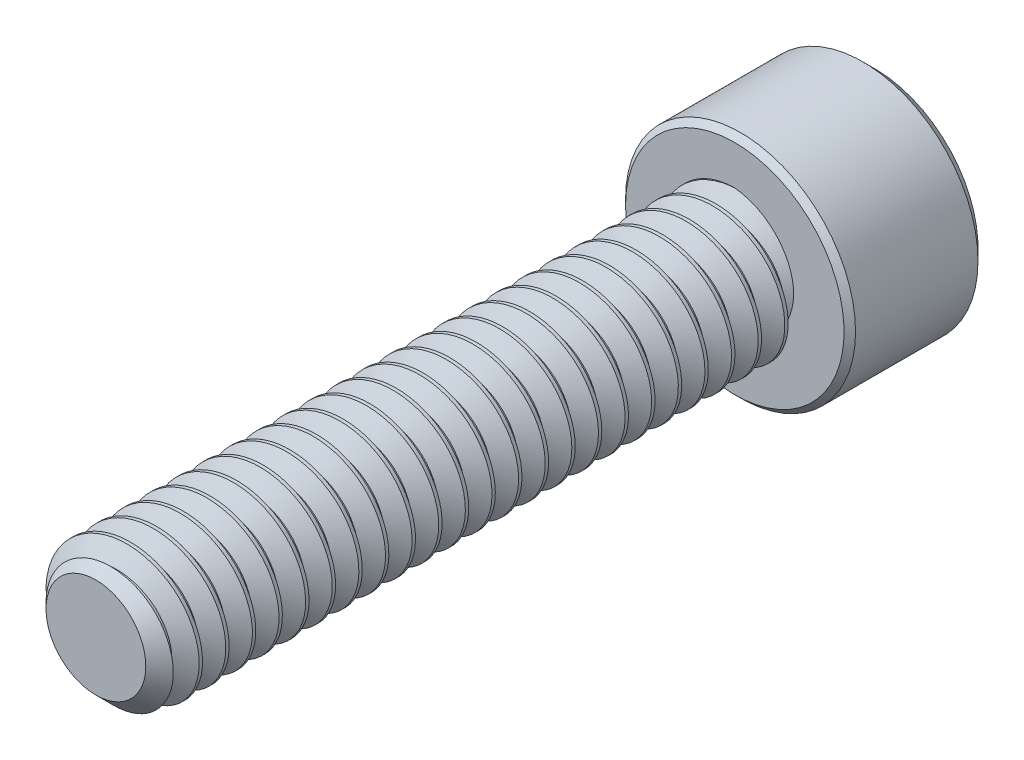
SolidWorks part; units mm, degrees
ref_plane "Front Plane" through (0, 0, 0) normal (0, 0, 1) x (1, 0, 0)
ref_plane "Top Plane" through (0, 0, 0) normal (0, 1, 0) x (1, 0, 0)
ref_plane "Right Plane" through (0, 0, 0) normal (1, 0, 0) x (0, 0, -1)
sketch "Sketch0" plane through (0, 0, 0) normal (1, 0, 0) x (0, 0, -1)
  line L0 (0, 0) -> (19.05, 0) construction
  point P2 (23.2156, 0)
  point P4 (0, 0)
  dimension "D1" = 19.05
  dimension "D2" = 4.1656
  dimension "Min Thread" = 0
sketch "Sketch1" plane through (0, 0, 0) normal (0, 0, 1) x (1, 0, 0)
  circle A0 centre (0, 0) radius 2.0828
  dimension "OD" = 4.1656
extrude "Extrude1" add sketch "Sketch1" against normal blind 19.05
sketch "Sketch2" plane through (0, 0, 0) normal (0, 0, 1) x (1, 0, 0)
  circle A0 centre (0, 0) radius 2.0828 construction
  circle A1 centre (0, 0) radius 2.0828
curve "Helix/Spiral1" pitch 0.7937 height 19.8438 turns 25 parameters "pitch"=0.7937
chamfer "Chamfer3" distance 0.5953 angle 45 1 edges at (2.0828, 0, 0)
sketch "Sketch3" plane through (0, 0, 0) normal (1, 0, 0) x (0, 0, -1)
  line L0 (-0.6945, 2.0828) -> (-0.3969, 1.5672)
  line L1 (-0.3969, 1.5672) -> (-0.2977, 1.5672)
  line L2 (-0.2977, 1.5672) -> (0, 2.0828)
  line L3 (-0.6945, 2.0828) -> (0, 2.0828)
  line L4 (-0.3473, 2.0828) -> (-0.3473, 1.5672) construction
  line L5 (-0.5457, 1.825) -> (-0.1488, 1.825) construction
  line L6 (0, 2.0828) -> (0, -2.0828) construction
  dimension "D1" = 0.0992
  dimension "D2" = 0.3969
  dimension "D3" = 60
sweep "Cut-Sweep1" cut profiles "Sketch3" path "Helix/Spiral1"
sketch "Sketch5" plane through (0, 0, 0) normal (1, 0, 0) x (0, 0, -1)
  line L0 (19.05, -1.5805) -> (19.05, 1.4861) construction
  line L1 (19.05, 2.0828) -> (0, 2.0828)
  line L2 (19.05, 2.0828) -> (19.05, 0)
  line L3 (19.05, 0) -> (-0.7581, 0)
  line L4 (0, 0) -> (19.05, 0) construction
  line L5 (0, 2.0828) -> (-0.7581, 0)
  line L6 (0, 0) -> (21.59, 0) construction
  dimension "D1" = 70
  dimension "D3" = 2.54
revolve "partially thread" [suppressed] add sketch "Sketch5" angle 360 about L6
sketch "Sketch6" plane through (0, 0, -19.05) normal (0, 0, -1) x (-1, 0, 0)
  circle A0 centre (0, 0) radius 3.429
  dimension "head dia" = 6.858
extrude "Extrude2" add sketch "Sketch6" along normal blind 4.1656
sketch "Sketch7" plane through (0, 0, -23.2156) normal (0, 0, -1) x (-1, 0, 0)
  line L1 (0, 2.0622) -> (-1.7859, 1.0311)
  line L2 (-1.7859, 1.0311) -> (-1.7859, -1.0311)
  line L3 (-1.7859, -1.0311) -> (0, -2.0622)
  line L4 (0, -2.0622) -> (1.7859, -1.0311)
  line L5 (1.7859, -1.0311) -> (1.7859, 1.0311)
  line L6 (1.7859, 1.0311) -> (0, 2.0622)
  circle A0 centre (0, 0) radius 1.7859 construction
  dimension "hex dia" = 3.5719
extrude "Cut-Extrude1" cut sketch "Sketch7" against normal blind 2.6789
sketch "Sketch8" plane through (0, 0, -23.2156) normal (0, 0, -1) x (-1, 0, 0)
  circle A0 centre (0, 0) radius 2.0622
extrude "Cut-Extrude2" cut sketch "Sketch8" against normal through all draft 45
chamfer "Chamfer1" distance 0.3429 angle 45 1 edges at (-3.429, 0, -23.2156)
chamfer "Chamfer2" distance 0.1715 angle 45 1 edges at (-3.429, 0, -19.05)
sketch "Sketch9" plane through (0, 0, 0) normal (1, 0, 0) x (0, 0, -1)
  line L0 (0, 2.0828) -> (0, -2.0828) construction
  line L1 (1.9844, 2.0828) -> (1.9844, -2.0828) construction
  line L2 (23.2156, 3.429) -> (23.2156, -3.429) construction
  line L3 (19.05, 3.429) -> (19.05, -3.429) construction
  line L4 (19.05, 3.2575) -> (19.05, -3.2575) construction
  line L5 (23.2156, -3.0861) -> (23.2156, 3.0861) construction
  line L6 (19.05, -3.429) -> (19.05, 3.429) construction
  line L7 (0, 1.4875) -> (0, -1.4875) construction
  line L8 (-0.6945, 2.0828) -> (0, 2.0828) construction
  line L9 (1.9844, 0) -> (0, 0) construction
  dimension "D1" = 1.9844
equation "\"D3@Helix/Spiral1\" = \"screw length@Extrude1\"+\"pitch@Helix/Spiral1\""
equation "\"D1@Sketch3\" = \"pitch@Helix/Spiral1\"*.125"
equation "\"D2@Sketch3\" = \"pitch@Helix/Spiral1\"*.5"
equation "\"D1@Cut-Extrude1\" = \"hex dia@Sketch7\"*.75"
equation "\"D1@Chamfer1\" = \"head dia@Sketch6\"*.05"
equation "\"D1@Sketch9\" = \"pitch@Helix/Spiral1\"*2.50"
equation "\"D1@Chamfer2\" = \"D1@Chamfer1\"/2"
equation "\"D1@Chamfer3\" = \"pitch@Helix/Spiral1\"*.750"
equation "\"D1@Sketch0\" = \"screw length@Extrude1\""
equation "\"D2@Sketch0\" = \"head depth@Extrude2\""
